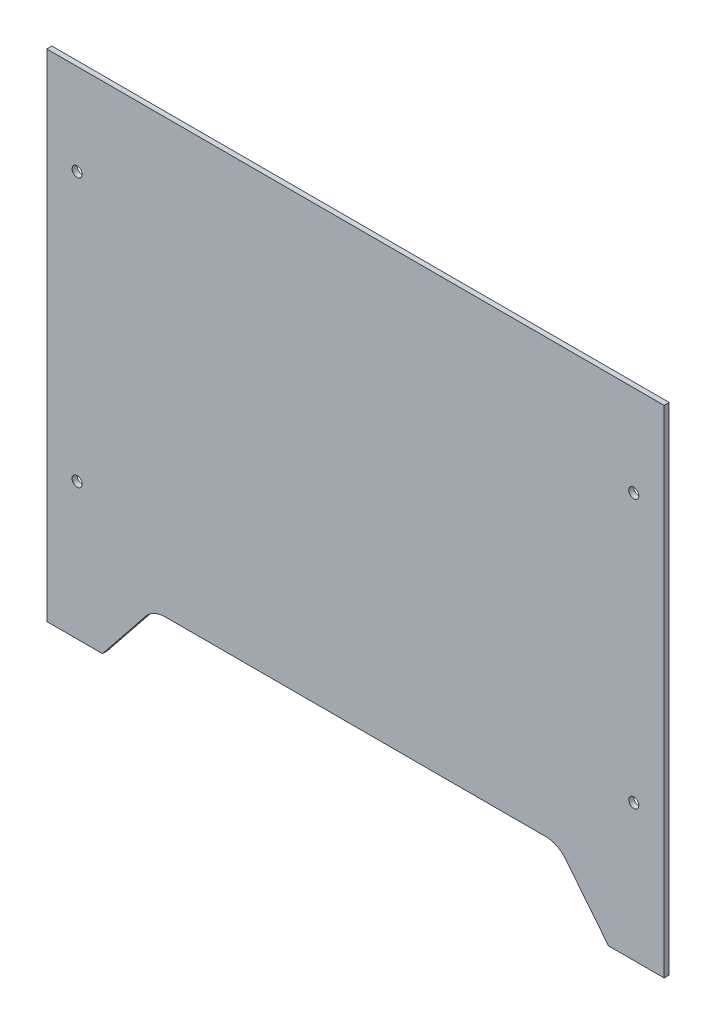
SolidWorks part; units mm, degrees
ref_plane "前视基准面" through (0, 0, 0) normal (0, 0, 1) x (1, 0, 0)
ref_plane "上视基准面" through (0, 0, 0) normal (0, 1, 0) x (1, 0, 0)
ref_plane "右视基准面" through (0, 0, 0) normal (1, 0, 0) x (0, 0, -1)
sketch "Sketch1" plane through (0, 0, 0) normal (0, 0, 1) x (1, 0, 0)
  line L0 (0, -98) -> (0, 0) construction
  line L1 (-122, -98) -> (122, -98) construction
  line L2 (-122, -98) -> (-122, 98)
  line L3 (-122, 98) -> (122, 98)
  line L4 (122, -98) -> (122, 98)
  line L5 (-122, -98) -> (122, 98) construction
  line L6 (-122, 98) -> (122, -98) construction
  line L7 (-75.1938, -73) -> (75.1938, -73)
  line L8 (83.0024, -76.753) -> (100, -98)
  line L9 (100, -98) -> (122, -98)
  line L10 (-100, -98) -> (-122, -98)
  line L11 (-83.0024, -76.753) -> (-100, -98)
  line L12 (110, -98) -> (110, 98) construction
  arc A0 (83.0024, -76.753) -> (75.1938, -73) centre (75.1938, -83) ccw
  arc A1 (-83.0024, -76.753) -> (-75.1938, -73) centre (-75.1938, -83) cw
  circle A2 centre (110, 62) radius 2
  circle A3 centre (110, -44) radius 2
  circle A4 centre (-110, -44) radius 2
  circle A5 centre (-110, 62) radius 2
  point P0 (0, 0)
  point P13 (80, -73)
  point P18 (0, -73)
  dimension "D6" = 10
  dimension "D8" = 4
  dimension "D9" = 4
  dimension "D1" = 244
  dimension "D2" = 196
  dimension "D3" = 25
  dimension "D4" = 22
  dimension "D5" = 80
  dimension "D7" = 12
  dimension "D10" = 36
  dimension "D11" = 106
extrude "Boss-Extrude1" add sketch "Sketch1" along normal blind 2
